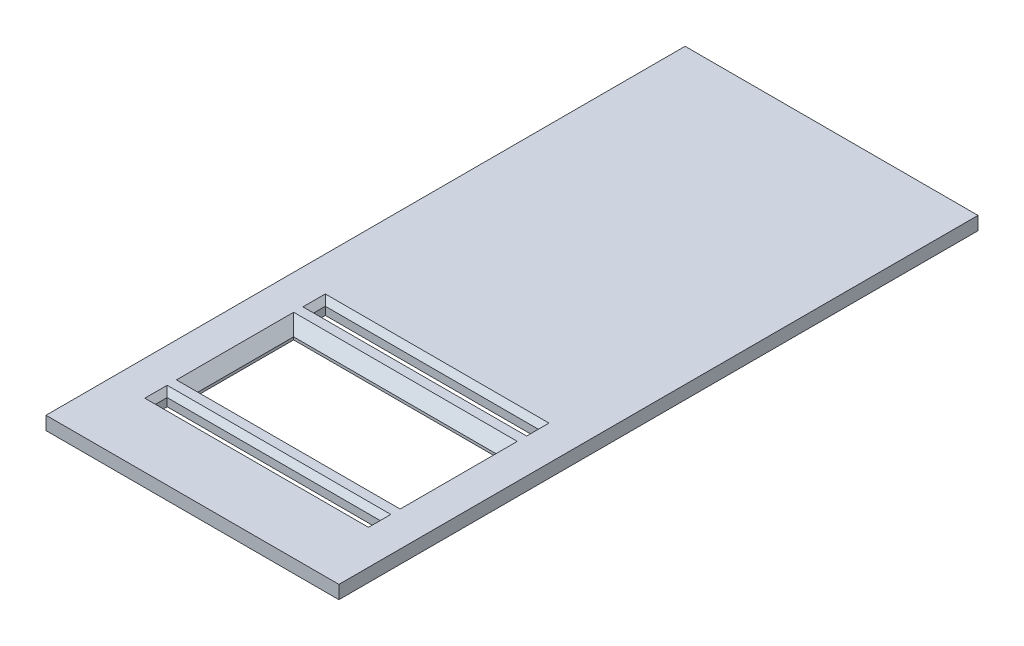
SolidWorks part; units mm, degrees
ref_plane "Front Plane" through (0, 0, 0) normal (0, 0, 1) x (1, 0, 0)
ref_plane "Top Plane" through (0, 0, 0) normal (0, 1, 0) x (1, 0, 0)
ref_plane "Right Plane" through (0, 0, 0) normal (1, 0, 0) x (0, 0, -1)
sketch "Sketch1" plane through (0, 0, 0) normal (0, 1, 0) x (1, 0, 0)
  line L1 (-69.85, -50.8) -> (69.85, -50.8)
  line L2 (-69.85, -50.8) -> (-69.85, 254)
  line L3 (-69.85, 254) -> (69.85, 254)
  line L4 (69.85, -50.8) -> (69.85, 254)
  line L5 (0, 254) -> (0, -50.8) construction
  line L6 (-69.85, 101.6) -> (69.85, 101.6) construction
  point P0 (0, 101.6)
  dimension "D1" = 304.8
  dimension "D2" = 139.7
  dimension "D3" = 101.6
extrude "Boss-Extrude1" add sketch "Sketch1" along normal blind 6.35
sketch "Sketch2" plane through (0, 6.35, 0) normal (0, 1, 0) x (1, 0, 0)
  line L0 (-69.85, -50.8) -> (69.85, -50.8) construction
  line L1 (-48.26, 0) -> (48.26, 0)
  line L2 (-48.26, 0) -> (-48.26, 45.72)
  line L3 (-48.26, 45.72) -> (48.26, 45.72)
  line L4 (48.26, 0) -> (48.26, 45.72)
  line L5 (0, 45.72) -> (0, 0) construction
  line L6 (-48.26, 22.86) -> (48.26, 22.86) construction
  point P0 (0, 22.86)
  dimension "D1" = 45.72
  dimension "D2" = 96.52
  dimension "D3" = 50.8
extrude "Main Hole" cut sketch "Sketch2" against normal through all
ref_plane "Plane1" through (0, 0, -22.86) normal (0, 0, 1) x (1, 0, 0)
sketch "Sketch3" plane through (0, 6.35, 0) normal (0, 1, 0) x (1, 0, 0)
  line L0 (48.26, 45.72) -> (-48.26, 45.72) construction
  line L1 (-50.8, 57.785) -> (50.8, 57.785)
  line L2 (-50.8, 57.785) -> (-50.8, 63.373)
  line L3 (-50.8, 63.373) -> (50.8, 63.373)
  line L4 (50.8, 57.785) -> (50.8, 63.373)
  point P4 (0, 57.785)
  dimension "D1" = 101.6
  dimension "D2" = 5.588
  dimension "D3" = 12.065
extrude "NeoPixel" cut sketch "Sketch3" against normal through all
mirror "Mirror2" about plane through (0, 0, -22.86) normal (0, 0, 1) of "NeoPixel"
sketch "Sketch5" plane through (0, 0, 0) normal (0, -1, 0) x (1, 0, 0)
  line L0 (69.85, -254) -> (-69.85, -254) construction
  line L1 (67.31, -251.46) -> (-67.31, -251.46)
  line L2 (67.31, -251.46) -> (67.31, 48.26)
  line L3 (67.31, 48.26) -> (-67.31, 48.26)
  line L4 (-67.31, -251.46) -> (-67.31, 48.26)
  line L5 (64.77, -248.92) -> (-64.77, -248.92)
  line L6 (64.77, -248.92) -> (64.77, 45.72)
  line L7 (64.77, 45.72) -> (-64.77, 45.72)
  line L8 (-64.77, -248.92) -> (-64.77, 45.72)
  line L9 (-69.85, -254) -> (-69.85, 50.8) construction
  line L10 (-69.85, 50.8) -> (69.85, 50.8) construction
  line L11 (69.85, 50.8) -> (69.85, -254) construction
  dimension "D1" = 2.54
  dimension "D2" = 2.54
  dimension "D3" = 2.54
  dimension "D4" = 2.54
  dimension "D5" = 2.54
  dimension "D6" = 2.54
  dimension "D7" = 2.54
  dimension "D8" = 2.54
extrude "Boss-Extrude2" add sketch "Sketch5" along normal blind 2.54 contours L4 L1 L2 L3 L5 L8 L7 L6 region at (0, 0, -251.1314)
chamfer "Chamfer1" distance 2.54 angle 45 8 edges at (50.8, 6.35, 14.859) (0, 6.35, 17.653) (-50.8, 6.35, 14.859) (0, 6.35, 12.065) (-50.8, 6.35, -60.579) (0, 6.35, -57.785) (50.8, 6.35, -60.579) (0, 6.35, -63.373)
chamfer "Chamfer2" distance 5.08 angle 45 4 edges at (48.26, 6.35, -22.86) (0, 6.35, 0) (-48.26, 6.35, -22.86) (0, 6.35, -45.72)
sketch "Sketch6" plane through (0, 0, 0) normal (0, -1, 0) x (1, 0, 0)
  line L0 (0.6985, -22.86) -> (-0.6985, -22.86) construction
  line L1 (50.8, 2.54) -> (-50.8, 2.54)
  line L2 (50.8, 2.54) -> (50.8, -48.26)
  line L3 (50.8, -48.26) -> (-50.8, -48.26)
  line L4 (-50.8, 2.54) -> (-50.8, -48.26)
  line L5 (0, -48.26) -> (0, 2.54) construction
  line L6 (50.8, -22.86) -> (-50.8, -22.86) construction
  line L7 (0, -3.4925) -> (0, 3.4925) construction
  line L8 (6.35, -50.8) -> (6.35, -48.26)
  line L9 (53.34, 5.08) -> (-53.34, 5.08)
  line L10 (53.34, 5.08) -> (53.34, -50.8)
  line L11 (53.34, -50.8) -> (-53.34, -50.8)
  line L12 (-53.34, 5.08) -> (-53.34, -50.8)
  line L13 (0, -50.8) -> (0, 5.08) construction
  line L14 (53.34, -22.86) -> (-53.34, -22.86) construction
  line L31 (-6.35, -50.8) -> (-6.35, -48.26)
  line L32 (6.35, -49.53) -> (-6.35, -49.53) construction
  point P0 (0, -22.86)
  point P8 (0, -22.86)
  point P16 (0, -49.53)
  dimension "D1" = 2.54
  dimension "D2" = 2.54
  dimension "D3" = 50.8
  dimension "D4" = 101.6
  dimension "D5" = 12.7
extrude "Boss-Extrude3" [suppressed] add sketch "Sketch6" along normal blind 4.064 contours L9 L12 L11 L10 L4 L1 L2 L3
equation "\"D1@Sketch2\"=1.8in"
equation "\"D2@Sketch2\"=3.8in"
